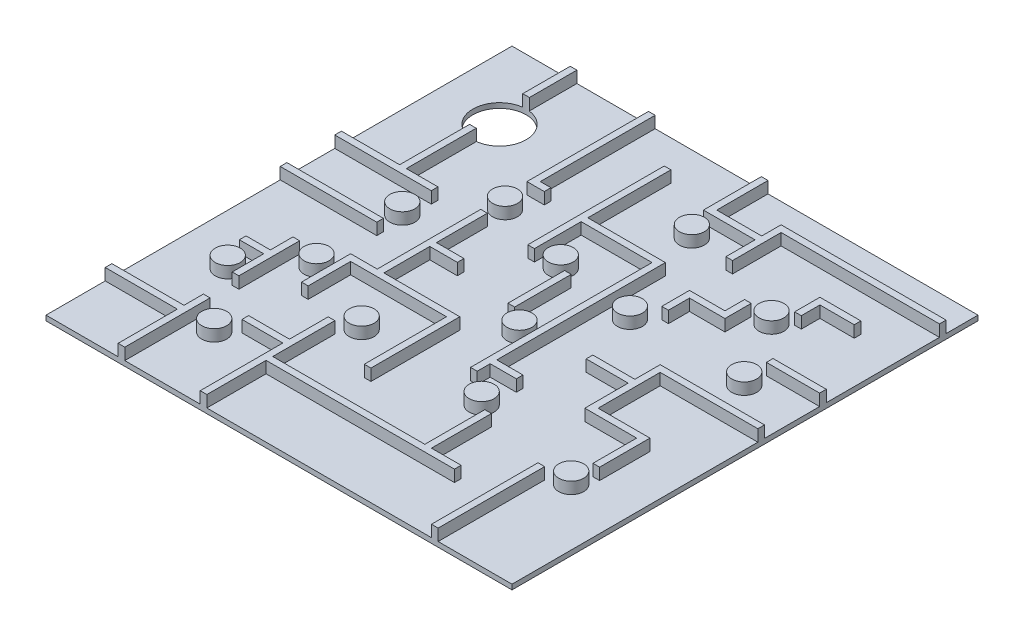
SolidWorks part; units mm, degrees
ref_plane "Front Plane" through (0, 0, 0) normal (0, 0, 1) x (1, 0, 0)
ref_plane "Top Plane" through (0, 0, 0) normal (0, 1, 0) x (1, 0, 0)
ref_plane "Right Plane" through (0, 0, 0) normal (1, 0, 0) x (0, 0, -1)
sketch "Sketch1" plane through (0, 0, 0) normal (0, 1, 0) x (1, 0, 0)
  line L1 (140, -140) -> (-140, -140)
  line L2 (140, -140) -> (140, 140)
  line L3 (140, 140) -> (-140, 140)
  line L4 (-140, -140) -> (-140, 140)
  line L5 (140, -140) -> (-140, 140) construction
  line L6 (140, 140) -> (-140, -140) construction
  circle A0 centre (-103, 95.5) radius 12.5 construction
  circle A2 centre (-103, 95.5) radius 16
  point P0 (0, 0)
  dimension "D2" = 25
  dimension "D4" = 24.5
  dimension "D5" = 32
  dimension "D3" = 32
  dimension "D1" = 280
extrude "Boss-Extrude1" add sketch "Sketch1" along normal mid plane 3
sketch "Sketch2" plane through (0, 1.5, 0) normal (0, 1, 0) x (1, 0, 0)
  line L0 (-139.5466, -22.5168) -> (140.7215, -22.5168) construction
  line L1 (-58, 140) -> (-58, 67)
  line L5 (-140, 140) -> (-140, -140)
  line L6 (-140, -140) -> (140, -140)
  line L7 (140, -140) -> (140, 140)
  line L8 (140, 140) -> (-140, 140)
  line L9 (-140, 140) -> (-140, -140) construction
  line L10 (-140, -140) -> (140, -140) construction
  line L11 (140, -140) -> (140, 140) construction
  line L12 (140, 140) -> (-140, 140) construction
  line L14 (-82, 33.5017) -> (-82, 4.7356) construction
  line L16 (-101, 140) -> (-105, 140)
  line L17 (-101, 140) -> (-101, 111.3745)
  line L19 (-105, 140) -> (-105, 111.3745)
  line L20 (-101, 140) -> (-105, 111.3745) construction
  line L21 (-101, 111.3745) -> (-105, 140) construction
  line L22 (-58, 67) -> (-47.6159, 67)
  line L23 (-47.6159, 67) -> (-47.6159, 71)
  line L24 (-47.6159, 71) -> (-54, 71)
  line L25 (-54, 71) -> (-54, 140)
  line L26 (-54, 140) -> (-58, 140)
  line L27 (-140, 37.5017) -> (-105, 37.5017)
  line L29 (-105, 37.5017) -> (-105, 79.6255)
  line L31 (-101, 37.5017) -> (-101, 79.6255)
  line L32 (-105, 37.5017) -> (-101, 79.6255) construction
  line L33 (-105, 79.6255) -> (-101, 37.5017) construction
  line L34 (-101, 37.5017) -> (-82, 37.5017)
  line L35 (-82, 37.5017) -> (-82, 33.5017)
  line L36 (-82, 33.5017) -> (-140, 33.5017)
  line L37 (-140, 33.5017) -> (-140, 37.5017)
  line L38 (-140, -100.4184) -> (-96.6685, -100.4184)
  line L39 (-140, 4.7356) -> (-82, 4.7356)
  line L40 (-140, 4.7356) -> (-140, 0.7356)
  line L41 (-140, 0.7356) -> (-82, 0.7356)
  line L42 (-82, 4.7356) -> (-82, 0.7356)
  line L43 (-96.6685, -100.4184) -> (-96.6685, -88.7386)
  line L44 (-96.6685, -88.7386) -> (-92.6685, -88.7386)
  line L45 (-92.6685, -88.7386) -> (-92.6685, -140)
  line L46 (-92.6685, -140) -> (-96.6685, -140)
  line L47 (-96.6685, -140) -> (-96.6685, -104.4184)
  line L48 (-96.6685, -104.4184) -> (-140, -104.4184)
  line L49 (-140, -104.4184) -> (-140, -100.4184)
  line L50 (-47.3451, -140) -> (-47.3451, -90.3646)
  line L51 (-47.3451, -90.3646) -> (-71.8819, -90.3646)
  line L52 (-71.8819, -90.3646) -> (-71.8819, -86.3646)
  line L53 (-71.8819, -86.3646) -> (-47.3451, -86.3646)
  line L54 (-47.3451, -86.3646) -> (-47.3451, -63.0886)
  line L55 (-47.3451, -63.0886) -> (-43.3451, -63.0886)
  line L56 (-43.3451, -63.0886) -> (-43.3451, -100.4184)
  line L57 (-43.3451, -100.4184) -> (48.0278, -100.4184)
  line L58 (48.0278, -100.4184) -> (48.0278, -64.3719)
  line L59 (48.0278, -64.3719) -> (52.0278, -64.3719)
  line L60 (52.0278, -64.3719) -> (52.0278, -100.4184)
  line L61 (52.0278, -100.4184) -> (69.8279, -100.4184)
  line L62 (69.8279, -100.4184) -> (69.8279, -104.4184)
  line L63 (69.8279, -104.4184) -> (-43.3451, -104.4184)
  line L64 (-43.3451, -104.4184) -> (-43.3451, -140)
  line L65 (-43.3451, -140) -> (-47.3451, -140)
  line L66 (140, 7.7373) -> (81.2931, 7.7373)
  line L67 (91.6226, -76) -> (95.6226, -76)
  line L68 (91.6226, -76) -> (91.6226, -140)
  line L69 (91.6226, -140) -> (95.6226, -140)
  line L70 (95.6226, -76) -> (95.6226, -140)
  line L71 (81.2931, 7.7373) -> (81.2931, -29.5435)
  line L72 (81.2931, -29.5435) -> (112.4312, -29.5435)
  line L73 (112.4312, -29.5435) -> (112.4312, -59.7773)
  line L74 (112.4312, -59.7773) -> (108.4312, -59.7773)
  line L75 (108.4312, -59.7773) -> (108.4312, -33.5435)
  line L76 (108.4312, -33.5435) -> (77.2931, -33.5435)
  line L77 (77.2931, -33.5435) -> (77.2931, -7.4768)
  line L78 (77.2931, -7.4768) -> (52.0278, -7.4768)
  line L79 (52.0278, -7.4768) -> (52.0278, -3.4768)
  line L80 (52.0278, -3.4768) -> (77.2931, -3.4768)
  line L81 (77.2931, -3.4768) -> (77.2931, 11.7373)
  line L82 (77.2931, 11.7373) -> (140, 11.7373)
  line L83 (140, 11.7373) -> (140, 7.7373)
  line L84 (-99.5107, -32.1119) -> (-95.5107, -32.1119)
  line L85 (140, 48.844) -> (108, 48.844)
  line L86 (140, 48.844) -> (140, 44.844)
  line L87 (140, 44.844) -> (108, 44.844)
  line L88 (108, 48.844) -> (108, 44.844)
  line L89 (-95.5107, -32.1119) -> (-95.5107, -68.5942)
  line L90 (-95.5107, -68.5942) -> (-99.5107, -68.5942)
  line L91 (-99.5107, -68.5942) -> (-99.5107, -49.6758)
  line L92 (-99.5107, -49.6758) -> (-114.1271, -49.6758)
  line L93 (-114.1271, -49.6758) -> (-114.1271, -45.6758)
  line L94 (-114.1271, -45.6758) -> (-99.5107, -45.6758)
  line L95 (-99.5107, -45.6758) -> (-99.5107, -32.1119)
  line L96 (-73.4352, -53.0425) -> (-69.4352, -53.0425)
  line L97 (-69.4352, -53.0425) -> (-69.4352, -27.5282)
  line L98 (-69.4352, -27.5282) -> (-11.8371, -27.5282)
  line L99 (-11.8371, -27.5282) -> (-11.8371, -76.9197)
  line L100 (-11.8371, -76.9197) -> (-7.8371, -76.9197)
  line L101 (-7.8371, -76.9197) -> (-7.8371, -23.5282)
  line L102 (-7.8371, -23.5282) -> (-53.4401, -23.5282)
  line L103 (-53.4401, -23.5282) -> (-53.4401, 4.0431)
  line L104 (-53.4401, 4.0431) -> (-36.8827, 4.0431)
  line L105 (-36.8827, 4.0431) -> (-36.8827, 8.0431)
  line L106 (-36.8827, 8.0431) -> (-53.4401, 8.0431)
  line L107 (-53.4401, 8.0431) -> (-53.4401, 38.6312)
  line L108 (-53.4401, 38.6312) -> (-57.4401, 38.6312)
  line L109 (-57.4401, 38.6312) -> (-57.4401, -23.5282)
  line L110 (-57.4401, -23.5282) -> (-73.4352, -23.5282)
  line L111 (-73.4352, -23.5282) -> (-73.4352, -53.0425)
  line L112 (114.8331, 94.8013) -> (114.8331, 90.8013)
  line L113 (-0.421, 32.0095) -> (3.579, 32.0095)
  line L114 (-0.421, 32.0095) -> (-0.421, -1.9905)
  line L115 (-0.421, -1.9905) -> (3.579, -1.9905)
  line L116 (3.579, 32.0095) -> (3.579, -1.9905)
  line L117 (114.8331, 90.8013) -> (94.2035, 90.8013)
  line L118 (94.2035, 90.8013) -> (94.2035, 79.6255)
  line L119 (94.2035, 79.6255) -> (90.2035, 79.6255)
  line L120 (90.2035, 79.6255) -> (90.2035, 94.8013)
  line L121 (90.2035, 94.8013) -> (114.8331, 94.8013)
  line L122 (68.7421, 71) -> (68.7421, 59.1986)
  line L123 (68.7421, 59.1986) -> (47.4471, 59.1986)
  line L124 (47.4471, 59.1986) -> (47.4471, 42.5547)
  line L125 (47.4471, 42.5547) -> (51.4471, 42.5547)
  line L126 (51.4471, 42.5547) -> (51.4471, 55.1986)
  line L127 (51.4471, 55.1986) -> (72.7421, 55.1986)
  line L128 (72.7421, 55.1986) -> (72.7421, 71)
  line L129 (72.7421, 71) -> (68.7421, 71)
  line L130 (21.7271, -46.6316) -> (25.7271, -46.6316)
  line L131 (25.7271, -46.6316) -> (25.7271, -38.8445)
  line L132 (25.7271, -38.8445) -> (41.4595, -38.8445)
  line L133 (41.4595, -38.8445) -> (41.4595, -34.8445)
  line L134 (41.4595, -34.8445) -> (25.7271, -34.8445)
  line L135 (25.7271, -34.8445) -> (25.7271, 66.4202)
  line L136 (25.7271, 66.4202) -> (-20.8726, 66.4202)
  line L137 (-20.8726, 66.4202) -> (-20.8726, 116.3442)
  line L138 (-20.8726, 116.3442) -> (-24.8726, 116.3442)
  line L139 (-24.8726, 116.3442) -> (-24.8726, 34.358)
  line L140 (-24.8726, 34.358) -> (-20.8726, 34.358)
  line L141 (-20.8726, 34.358) -> (-20.8726, 62.4202)
  line L142 (-20.8726, 62.4202) -> (21.7271, 62.4202)
  line L143 (21.7271, 62.4202) -> (21.7271, -46.6316)
  line L144 (140, 116.8451) -> (44.8417, 116.8451)
  line L145 (44.8417, 116.8451) -> (44.8417, 87.6566)
  line L146 (44.8417, 87.6566) -> (40.8417, 87.6566)
  line L147 (40.8417, 87.6566) -> (40.8417, 105.182)
  line L148 (40.8417, 105.182) -> (9.8488, 105.182)
  line L149 (9.8488, 105.182) -> (9.8488, 140)
  line L150 (9.8488, 140) -> (13.8488, 140)
  line L151 (13.8488, 140) -> (13.8488, 109.182)
  line L152 (13.8488, 109.182) -> (40.8417, 109.182)
  line L153 (40.8417, 109.182) -> (40.8417, 120.8451)
  line L154 (40.8417, 120.8451) -> (140, 120.8451)
  line L155 (140, 120.8451) -> (140, 116.8451)
  circle A0 centre (-103, 95.5) radius 16 construction
  circle A1 centre (-103, 95.5) radius 16 construction
  arc A4 (-101, 111.3745) -> (-105, 111.3745) centre (-103, 95.5) ccw
  arc A5 (-101, 79.6255) -> (-105, 79.6255) centre (-103, 95.5) cw
  circle A6 centre (-56.9927, 52.7967) radius 7.5
  circle A7 centre (-85.015, 19.1186) radius 7.5
  circle A8 centre (-83.7389, -33.6905) radius 7.5
  circle A9 centre (-109.5163, -61.2699) radius 7.5
  circle A10 centre (-80.6927, -98.2301) radius 7.5
  circle A11 centre (-37.7057, -52.6278) radius 7.5
  circle A12 centre (37.5874, -55.832) radius 7.5
  circle A13 centre (105.9105, -70.3332) radius 7.5
  circle A14 centre (11.8193, -7.3525) radius 7.5
  circle A15 centre (-9.7559, 39.067) radius 7.5
  circle A16 centre (13.8835, 94.1998) radius 7.5
  circle A17 centre (82.6249, 73.2846) radius 7.5
  circle A18 centre (37.5874, 33.2669) radius 7.5
  circle A19 centre (106.2527, 33.2879) radius 7.5
  point P9 (-82, 19.1186)
  point P10 (-30.3505, -51.3202)
  point P11 (-39.0133, -53.0425)
  point P12 (-28.8794, -61.2699)
  point P13 (-80.3658, -98.3935)
  point P14 (-103, 125.6873)
  point P21 (-103, 58.5636)
  point P66 (93.6226, -76)
  dimension "D6" = 29
  dimension "D8" = 15
  dimension "D52" = 15
  dimension "D53" = 15
  dimension "D54" = 15
  dimension "D55" = 15
  dimension "D56" = 15
  dimension "D57" = 15
  dimension "D58" = 15
  dimension "D59" = 15
  dimension "D60" = 15
  dimension "D61" = 15
  dimension "D62" = 15
  dimension "D63" = 15
  dimension "D64" = 15
  dimension "D1" = 0
  dimension "D3" = 4
  dimension "D4" = 4
  dimension "D5" = 4
  dimension "D7" = 69
  dimension "D9" = 4
  dimension "D10" = 4
  dimension "D11" = 58
  dimension "D12" = 4
  dimension "D13" = 58
  dimension "D14" = 4
  dimension "D15" = 4
  dimension "D16" = 4
  dimension "D17" = 4
  dimension "D18" = 4
  dimension "D19" = 4
  dimension "D20" = 4
  dimension "D21" = 4
  dimension "D22" = 64
  dimension "D23" = 4
  dimension "D24" = 4
  dimension "D25" = 4
  dimension "D26" = 4
  dimension "D27" = 4
  dimension "D28" = 4
  dimension "D29" = 32
  dimension "D30" = 4
  dimension "D31" = 4
  dimension "D32" = 4
  dimension "D33" = 4
  dimension "D34" = 4
  dimension "D35" = 4
  dimension "D36" = 4
  dimension "D37" = 4
  dimension "D38" = 34
  dimension "D39" = 4
  dimension "D40" = 4
  dimension "D41" = 4
  dimension "D42" = 4
  dimension "D43" = 4
  dimension "D44" = 4
  dimension "D45" = 4
  dimension "D46" = 4
  dimension "D47" = 4
  dimension "D48" = 4
  dimension "D49" = 4
  dimension "D50" = 4
  dimension "D51" = 4
extrude "Boss-Extrude2" add sketch "Sketch2" along normal blind 7
sketch "Sketch4" plane through (0, 1.5, 0) normal (0, 1, 0) x (1, 0, 0)
  line L0 (-105, 140) -> (-140, 140) construction
  line L1 (-111.0554, 140) -> (-95.4557, 140)
  line L2 (-111.0554, 140) -> (-111.0554, 108.084)
  line L3 (-111.0554, 108.084) -> (-95.4557, 108.084)
  line L4 (-95.4557, 140) -> (-95.4557, 108.084)
  line L5 (5.9631, 143.7406) -> (7.9794, 102.774)
  line L6 (-147.4549, 88.7508) -> (-77.515, 88.7508)
  line L7 (-147.4549, 88.7508) -> (-147.4549, 30.0852)
  line L8 (-147.4549, 30.0852) -> (-77.515, 30.0852)
  line L9 (-77.515, 88.7508) -> (-77.515, 30.0852)
  line L10 (-67.599, 143.7406) -> (-41.5994, 143.7406)
  line L11 (-67.599, 143.7406) -> (-67.599, 63.1419)
  line L12 (-67.599, 63.1419) -> (-41.5994, 63.1419)
  line L13 (-41.5994, 143.7406) -> (-41.5994, 63.1419)
  line L14 (-147.4549, 7.7999) -> (-80.2273, 7.7999)
  line L15 (-147.4549, 7.7999) -> (-147.4549, -3.3428)
  line L16 (-147.4549, -3.3428) -> (-80.2273, -3.3428)
  line L17 (-80.2273, 7.7999) -> (-80.2273, -3.3428)
  line L18 (-147.4549, -83.9416) -> (-90.2557, -83.9416)
  line L19 (-147.4549, -83.9416) -> (-147.4549, -144.4835)
  line L20 (-147.4549, -144.4835) -> (-90.2557, -144.4835)
  line L21 (-90.2557, -83.9416) -> (-90.2557, -144.4835)
  line L22 (97.7216, -74.6829) -> (89.8032, -74.6829)
  line L23 (97.7216, -74.6829) -> (97.7216, -144.4835)
  line L24 (97.7216, -144.4835) -> (89.8032, -144.4835)
  line L25 (89.8032, -74.6829) -> (89.8032, -144.4835)
  line L26 (143.8995, -60.5264) -> (51.0585, -60.5264)
  line L27 (143.8995, -60.5264) -> (143.8995, 16.1793)
  line L28 (143.8995, 16.1793) -> (51.0585, 16.1793)
  line L29 (51.0585, -60.5264) -> (51.0585, 16.1793)
  line L30 (88.927, 78.8767) -> (116.5902, 78.8767)
  line L31 (88.927, 78.8767) -> (88.927, 97.3845)
  line L32 (88.927, 97.3845) -> (116.5902, 97.3845)
  line L33 (116.5902, 78.8767) -> (116.5902, 97.3845)
  line L34 (73.3744, 72.1075) -> (45.9857, 72.1075)
  line L35 (73.3744, 72.1075) -> (73.3744, 41.1619)
  line L36 (73.3744, 41.1619) -> (45.9857, 41.1619)
  line L37 (45.9857, 72.1075) -> (45.9857, 41.1619)
  line L38 (105.2092, 50.41) -> (142.3795, 50.41)
  line L39 (105.2092, 50.41) -> (105.2092, 43.6518)
  line L40 (105.2092, 43.6518) -> (142.3795, 43.6518)
  line L41 (142.3795, 50.41) -> (142.3795, 43.6518)
  line L42 (7.9794, 102.774) -> (36.2066, 102.774)
  line L43 (36.2066, 102.774) -> (36.2066, 85.384)
  line L44 (36.2066, 85.384) -> (47.7999, 85.384)
  line L45 (47.7999, 85.384) -> (47.7999, 114.3673)
  line L46 (47.7999, 114.3673) -> (142.3795, 114.3673)
  line L47 (142.3795, 114.3673) -> (142.3795, 146.3749)
  line L48 (142.3795, 146.3749) -> (5.9631, 143.7406)
  line L49 (45.9857, -63.0608) -> (55.6128, -63.0608)
  line L50 (55.6128, -63.0608) -> (55.6128, -94.5644)
  line L51 (55.6128, -94.5644) -> (73.3744, -98.5969)
  line L52 (73.3744, -98.5969) -> (71.3652, -107.4466)
  line L53 (71.3652, -107.4466) -> (-50.2392, -144.4835)
  line L54 (-50.2392, -144.4835) -> (-51.2032, -94.5644)
  line L55 (-51.2032, -94.5644) -> (-74.182, -91.5401)
  line L56 (-74.182, -91.5401) -> (-74.182, -83.9416)
  line L57 (-74.182, -83.9416) -> (-51.2032, -83.9416)
  line L58 (-51.2032, -83.9416) -> (-51.2032, -60.5264)
  line L59 (-51.2032, -60.5264) -> (-41.5994, -61.7904)
  line L60 (-41.5994, -61.7904) -> (-39.8871, -96.5806)
  line L61 (-39.8871, -96.5806) -> (42.0032, -96.5806)
  line L62 (42.0032, -96.5806) -> (45.9857, -63.0608)
  line L63 (-5.6302, -79.1855) -> (-16.4674, -79.1855)
  line L64 (-16.4674, -79.1855) -> (-16.4674, -32.0613)
  line L65 (-16.4674, -32.0613) -> (-66.3537, -32.0613)
  line L66 (-66.3537, -32.0613) -> (-66.3537, -52.7277)
  line L67 (-66.3537, -52.7277) -> (-69.4859, -55.8599)
  line L68 (-69.4859, -55.8599) -> (-74.182, -55.8599)
  line L69 (-74.182, -55.8599) -> (-74.182, -19.9639)
  line L70 (-74.182, -19.9639) -> (-60.8244, -19.9639)
  line L71 (-60.8244, -19.9639) -> (-60.8244, 41.1619)
  line L72 (-60.8244, 41.1619) -> (-50.7212, 41.1619)
  line L73 (-50.7212, 41.1619) -> (-5.6302, -25.2565)
  line L74 (-5.6302, -25.2565) -> (-5.6302, -79.1855)
  line L75 (-95.4557, -29.8902) -> (-93.4806, -70.0213)
  line L76 (-93.4806, -70.0213) -> (-101.149, -70.0213)
  line L77 (-101.149, -70.0213) -> (-101.149, -52.7277)
  line L78 (-101.149, -52.7277) -> (-115.689, -51.0001)
  line L79 (-115.689, -51.0001) -> (-115.689, -42.3945)
  line L80 (-115.689, -42.3945) -> (-103.4173, -42.3945)
  line L81 (-103.4173, -42.3945) -> (-101.9316, -29.8902)
  line L82 (-101.9316, -29.8902) -> (-95.4557, -29.8902)
  line L83 (-28.4925, 119.5346) -> (-16.4674, 117.756)
  line L84 (-1.8935, 32.9846) -> (4.3847, 32.9846)
  line L85 (-1.8935, 32.9846) -> (-1.8935, -2.8259)
  line L86 (-1.8935, -2.8259) -> (4.3847, -2.8259)
  line L87 (4.3847, 32.9846) -> (4.3847, -2.8259)
  line L88 (-16.4674, 117.756) -> (-16.4674, 69.1408)
  line L89 (-16.4674, 69.1408) -> (27.2371, 69.1408)
  line L90 (27.2371, 69.1408) -> (27.2371, -32.0613)
  line L91 (27.2371, -32.0613) -> (45.9857, -32.0613)
  line L92 (45.9857, -32.0613) -> (43.134, -41.9421)
  line L93 (43.134, -41.9421) -> (27.2371, -41.9421)
  line L94 (27.2371, -41.9421) -> (27.2371, -51.0001)
  line L95 (27.2371, -51.0001) -> (17.9746, -49.6302)
  line L96 (17.9746, -49.6302) -> (19.7304, -15.8544)
  line L97 (19.7304, -15.8544) -> (20.3739, 2.1642)
  line L98 (20.3739, 2.1642) -> (18.5332, 38.2959)
  line L99 (18.5332, 38.2959) -> (-16.8954, 50.706)
  line L100 (-16.8954, 50.706) -> (-19.4975, 31.4904)
  line L101 (-19.4975, 31.4904) -> (-28.3046, 32.0909)
  line L102 (-28.3046, 32.0909) -> (-28.4925, 119.5346)
  line L104 (-67.0582, 61.2608) -> (-47.0319, 61.2608)
  line L105 (-67.0582, 61.2608) -> (-67.0582, 43.6518)
  line L106 (-67.0582, 43.6518) -> (-47.0319, 43.6518)
  line L107 (-47.0319, 61.2608) -> (-47.0319, 43.6518)
